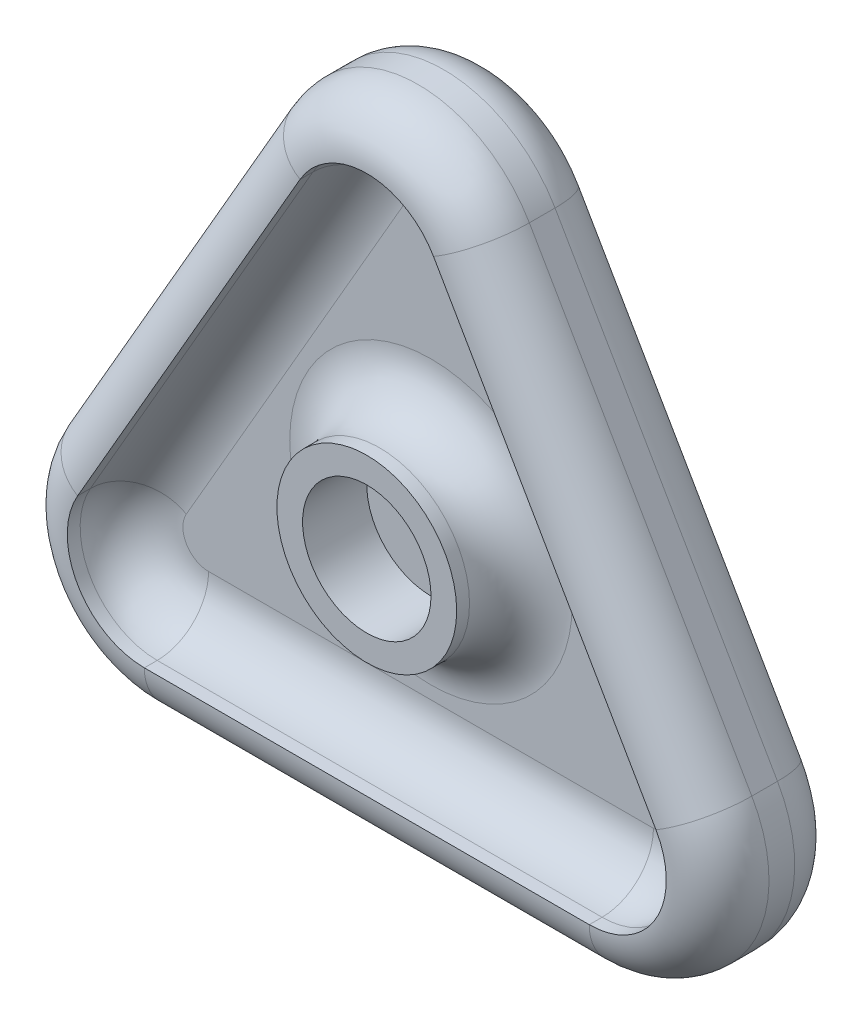
SolidWorks part; units mm, degrees
ref_plane "前视基准面" through (0, 0, 0) normal (0, 0, 1) x (1, 0, 0)
ref_plane "上视基准面" through (0, 0, 0) normal (0, 1, 0) x (1, 0, 0)
ref_plane "右视基准面" through (0, 0, 0) normal (1, 0, 0) x (0, 0, -1)
sketch "草图2" plane through (0, 0, 0) normal (0, 0, 1) x (1, 0, 0)
  line L1 (12.9904, -2.5) -> (4.3301, 12.5)
  line L2 (-4.3301, 12.5) -> (-12.9904, -2.5)
  line L3 (-8.6603, -10) -> (8.6603, -10)
  circle A0 centre (0, 0) radius 10 construction
  arc A1 (12.9904, -2.5) -> (8.6603, -10) centre (8.6603, -5) cw
  arc A2 (-12.9904, -2.5) -> (-8.6603, -10) centre (-8.6603, -5) ccw
  arc A3 (4.3301, 12.5) -> (-4.3301, 12.5) centre (0, 10) ccw
  dimension "D1" = 20
  dimension "D2" = 5
extrude "凸台-拉伸1" add sketch "草图2" along normal blind 5
sketch "草图3" plane through (0, 0, 5) normal (0, 0, 1) x (1, 0, 0)
  line L6 (11.2583, -3.5) -> (2.5981, 11.5)
  line L7 (-2.5981, 11.5) -> (-11.2583, -3.5)
  line L8 (-8.6603, -8) -> (8.6603, -8)
  line L9 (11.2583, -3.5) -> (2.5981, 11.5)
  line L10 (-2.5981, 11.5) -> (-11.2583, -3.5)
  line L11 (-8.6603, -8) -> (8.6603, -8)
  arc A6 (8.6603, -8) -> (11.2583, -3.5) centre (8.6603, -5) ccw
  arc A7 (2.5981, 11.5) -> (-2.5981, 11.5) centre (0, 10) ccw
  arc A8 (-11.2583, -3.5) -> (-8.6603, -8) centre (-8.6603, -5) ccw
  arc A9 (8.6603, -8) -> (11.2583, -3.5) centre (8.6603, -5) ccw
  arc A10 (2.5981, 11.5) -> (-2.5981, 11.5) centre (0, 10) ccw
  arc A11 (-11.2583, -3.5) -> (-8.6603, -8) centre (-8.6603, -5) ccw
  dimension "D1" = 2
extrude "切除-拉伸1" cut sketch "草图3" against normal blind 2.5
sketch "草图4" plane through (0, 0, 2.5) normal (0, 0, 1) x (1, 0, 0)
  circle A0 centre (0, 0) radius 2.5
  circle A1 centre (0, 0) radius 3.5
  dimension "D1" = 5
  dimension "D2" = 7
extrude "凸台-拉伸2" add sketch "草图4" along normal blind 2.5
fillet "圆角1" radius 2 6 edges at (-12.9904, -7.5, 5) (-8.6603, 5, 5) (0, 15, 5) (8.6603, 5, 5) (12.9904, -7.5, 5) (0, -10, 5)
fillet "圆角2" radius 2 7 edges at (0, -8, 2.5) (-11.2583, -6.5, 2.5) (-6.9282, 4, 2.5) (0, 13, 2.5) (6.9282, 4, 2.5) (11.2583, -6.5, 2.5) (3.5, 0, 2.5)
fillet "圆角3" radius 2 6 edges at (8.6603, 5, 0) (0, 15, 0) (-8.6603, 5, 0) (-12.9904, -7.5, 0) (0, -10, 0) (12.9904, -7.5, 0)
scale "缩放比例1" bodies to scale 103 scale about centroid uniform scaling yes scale factor 2
